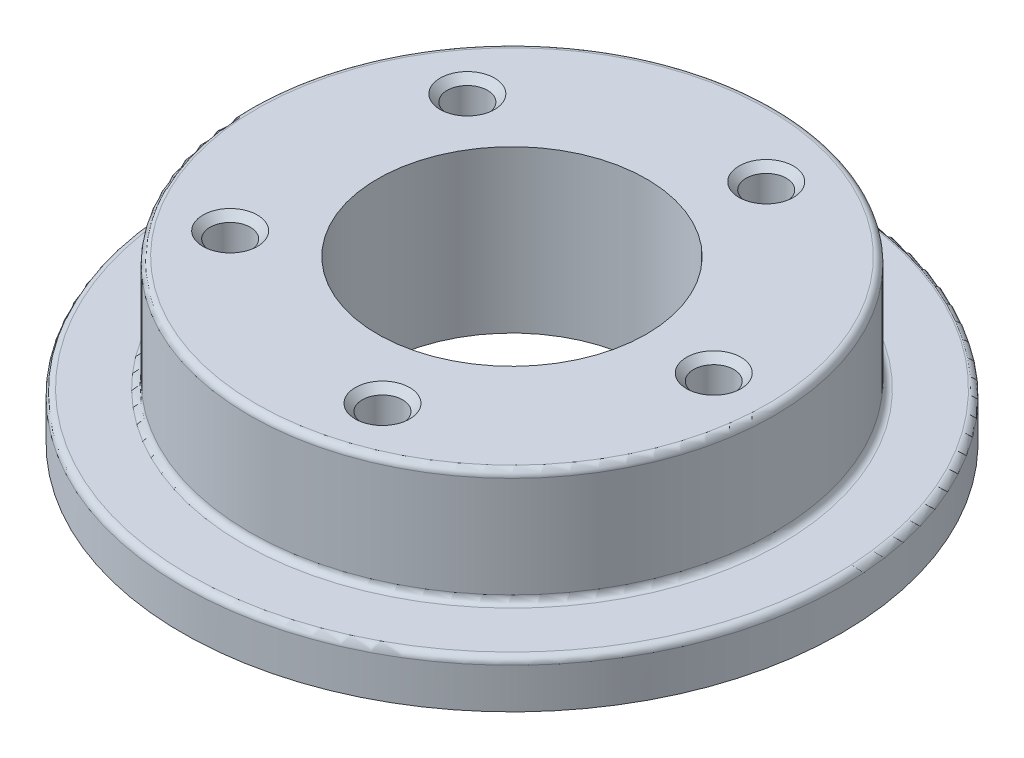
SolidWorks part; units mm, degrees
ref_plane "Front" through (0, 0, 0) normal (0, 0, 1) x (1, 0, 0)
ref_plane "Top" through (0, 0, 0) normal (0, 1, 0) x (1, 0, 0)
ref_plane "Right" through (0, 0, 0) normal (1, 0, 0) x (0, 0, -1)
sketch "Sketch1" plane through (0, 0, 0) normal (0, 1, 0) x (1, 0, 0)
  circle A0 centre (0, 0) radius 24.5
  circle A1 centre (0, 0) radius 19.5
  circle A2 centre (0, 0) radius 10
  dimension "D1" = 49
  dimension "D2" = 39
  dimension "D3" = 20
extrude "Extrude1" add sketch "Sketch1" along normal blind 3.5 contours A0 | A2
extrude "Extrude2" add sketch "Sketch1<3>" along normal blind 12 contours A1 | A2
sketch "Sketch1<3>" plane through (0, 0, 0) normal (0, 1, 0) x (1, 0, 0) same geometry as "Sketch1"
hole_wizard "Ø3.0 Diameter Hole1" positions "3DSketch1" profile "Sketch3" hole size "Ø3.0" standard "Ansi Metric"
sketch3d "3DSketch1"
  line L4 (0, 12, 0) -> (15, 12, 0) construction
  line L5 (0, 12, 0) -> (0, 3.5, 0) construction
  point P6 (15, 12, 0)
  dimension "D1" = 15
sketch "Sketch3" plane through (15, 12, 0) normal (1, 0, 0) x (0, 0, 1)
  line L0 (0, 0) -> (0, 10.9013)
  line L1 (0, 10.9013) -> (1.5, 10)
  line L2 (1.5, 10) -> (1.5, 0.525)
  line L3 (1.5, 0.525) -> (2.025, 0)
  line L5 (2.025, 0) -> (0, 0)
  line L6 (-1.5, 0.525) -> (-2.025, 0) construction
  line L10 (0, 10.9013) -> (-1.5, 10) construction
  line L11 (0, -6.35) -> (0, 107.95) construction
  dimension "Hole Dia." = 3
  dimension "Hole Depth" = 10
  dimension "Near C'Sink Dia." = 4.05
  dimension "Near C'Sink Angle" = 90
  dimension "Drill Angle" = 118
pattern_circular "CirPattern1" count 5 over 360 about axis through (0, 12, 0) along (0, -1, 0) of "Ø3.0 Diameter Hole1"
fillet "Finishing Fillet" radius 0.5 3 edges at (19.5, 12, 0) (0, 3.5, 19.5) (24.5, 3.5, 0)
sketch "Çizim1" plane through (0, 12, 0) normal (0, 1, 0) x (1, 0, 0)
  line L0 (0, 28.5765) -> (0, -44.2609) construction
  line L1 (-47.9938, 0) -> (43.0877, 0) construction
  point P0 (0, 0)
sketch "Çizim2" plane through (0, 0, 0) normal (1, 0, 0) x (0, 0, -1)
  line L0 (0, 22.6012) -> (0, -16.9817) construction
